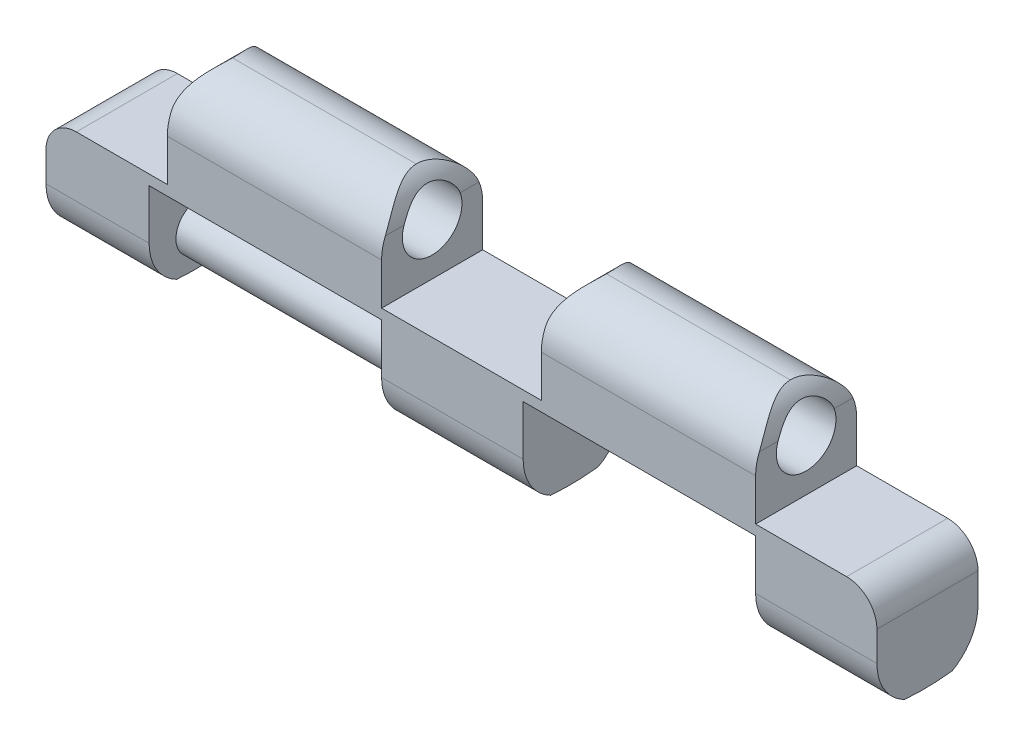
SolidWorks part; units mm, degrees
ref_plane "Alzado" through (0, 0, 0) normal (0, 0, 1) x (1, 0, 0)
ref_plane "Planta" through (0, 0, 0) normal (0, 1, 0) x (1, 0, 0)
ref_plane "Vista lateral" through (0, 0, 0) normal (1, 0, 0) x (0, 0, -1)
sketch "Croquis1" plane through (0, 0, 0) normal (0, 0, 1) x (1, 0, 0)
  line L0 (-11.2351, 0) -> (-5.2351, 0)
  line L1 (-5.2351, 0) -> (-5.2351, 3)
  line L2 (-3.2351, 5) -> (3.3649, 5)
  line L3 (5.3649, 3) -> (5.3649, 0)
  line L4 (5.3649, 0) -> (13.2649, 0)
  line L5 (13.2649, 0) -> (13.2649, 3)
  line L6 (15.2649, 5) -> (21.8649, 5)
  line L7 (23.8649, 3) -> (23.8649, 0)
  line L8 (23.8649, 0) -> (29.8649, 0)
  line L9 (29.8649, 0) -> (29.8649, -6)
  line L10 (29.8649, -6) -> (23.8649, -6)
  line L14 (12.3649, -6) -> (5.3649, -6)
  line L15 (5.3649, -6) -> (5.3649, -0.5)
  line L16 (5.3649, -0.5) -> (-6.1351, -0.5)
  line L17 (-6.1351, -0.5) -> (-6.1351, -6)
  line L18 (-6.1351, -6) -> (-11.2351, -6)
  line L19 (-11.2351, -6) -> (-11.2351, 0)
  line L20 (12.3649, -6) -> (12.3649, -0.5)
  line L21 (12.3649, -0.5) -> (23.8649, -0.5)
  line L22 (23.8649, -0.5) -> (23.8649, -6)
  arc A0 (-5.2351, 3) -> (-3.2351, 5) centre (-3.2351, 3) cw
  arc A1 (3.3649, 5) -> (5.3649, 3) centre (3.3649, 3) cw
  arc A2 (13.2649, 3) -> (15.2649, 5) centre (15.2649, 3) cw
  arc A3 (21.8649, 5) -> (23.8649, 3) centre (21.8649, 3) cw
  point P25 (-5.2351, 5)
  point P28 (5.3649, 5)
  point P31 (13.2649, 5)
  point P34 (23.8649, 5)
  dimension "D14" = 2
  dimension "D15" = 2
  dimension "D16" = 2
  dimension "D17" = 2
  dimension "D1" = 6
  dimension "D2" = 5
  dimension "D3" = 10.6
  dimension "D4" = 5.5
  dimension "D5" = 5
  dimension "D6" = 10.6
  dimension "D7" = 6
  dimension "D10" = 7.9
  dimension "D11" = 6
  dimension "D12" = 6
  dimension "D13" = 11.5
extrude "Saliente-Extruir1" add sketch "Croquis1" along normal blind 5
sketch "Croquis22" plane through (5.3649, 0, 0) normal (1, 0, 0) x (0, 0, -1)
  line L0 (-5, 5) -> (0, 5) construction
  line L2 (-5, 0) -> (-5, 3) construction
  circle A0 centre (-2.5, 2.5) radius 1.475
  dimension "D3" = 2.95
  dimension "D1" = 2.5
  dimension "D2" = 2.5
extrude "Cortar-Extruir19" cut sketch "Croquis22" against normal blind 11.5
sketch "Croquis23" plane through (23.8649, 0, 0) normal (1, 0, 0) x (0, 0, -1)
  line L0 (-5, 5) -> (0, 5) construction
  line L1 (-5, 0) -> (-5, 3) construction
  circle A0 centre (-2.5, 2.5) radius 1.475
  dimension "D1" = 2.95
  dimension "D2" = 2.5
  dimension "D3" = 2.5
extrude "Cortar-Extruir20" cut sketch "Croquis23" against normal blind 11.5
sketch "Croquis24" plane through (23.8649, 0, 0) normal (1, 0, 0) x (0, 0, -1)
  arc A0 (-5.6425, 3.2539) -> (0.6953, 3.2539) centre (-2.4736, 0.085) cw
extrude "Cortar-Extruir21" cut sketch "Croquis24" against normal through all and the other way through all
sketch "Croquis25" plane through (-6.1351, 0, 0) normal (1, 0, 0) x (0, 0, -1)
sketch "Croquis26" plane through (-6.1351, 0, 0) normal (1, 0, 0) x (0, 0, -1)
  line L0 (-5, -0.5) -> (0, -0.5) construction
  line L1 (-5, -6) -> (-5, -0.5) construction
  circle A0 centre (-2.5, -3.45) radius 1.175
  dimension "D3" = 2.35
  dimension "D1" = 2.95
  dimension "D2" = 2.5
sketch "Croquis27" plane through (12.3649, 0, 0) normal (1, 0, 0) x (0, 0, -1)
  line L0 (-5, -0.5) -> (0, -0.5) construction
  line L1 (-5, -6) -> (-5, -0.5) construction
  circle A0 centre (-2.5, -3.45) radius 1.175
  dimension "D3" = 2.35
  dimension "D1" = 2.95
  dimension "D2" = 2.5
sketch "Croquis28" plane through (29.8649, 0, 0) normal (1, 0, 0) x (0, 0, -1)
  arc A0 (-5.5986, -4.9472) -> (0.708, -4.9472) centre (-2.4453, 4.2661) ccw
extrude "Cortar-Extruir23" cut sketch "Croquis28" against normal through all and the other way through all flip side to cut
fillet "Redondeo10" radius 2.5 10 edges at (-8.6851, -5.1308, 5) (-8.6851, -5.1598, 0) (8.8649, -5.1308, 5) (8.8649, -5.1598, 0) (26.8649, -5.1598, 0) (26.8649, -5.1308, 5) (0.0649, 3.7865, 5) (0.0649, 3.822, 0) (18.5649, 3.822, 0) (18.5649, 3.7865, 5)
sketch "Croquis14" plane through (23.8649, 0, 0) normal (1, 0, 0) x (0, 0, -1)
  line L0 (0, 0) -> (0, 2.0664) construction
  line L1 (-5, 0) -> (0, 0) construction
  circle A0 centre (-2.5, 2.5) radius 1.475
  dimension "D1" = 2.95
  dimension "D2" = 2.5
  dimension "D3" = 2.5
fillet "Redondeo6" radius 1.5 2 edges at (29.8649, 0, 2.5) (-11.2351, 0, 2.5)
sketch "Croquis19" plane through (29.8649, 0, 0) normal (1, 0, 0) x (0, 0, -1)
sketch "Croquis21" plane through (29.8649, 0, 0) normal (1, 0, 0) x (0, 0, -1)
  arc A0 (-6.0352, -4.762) -> (0.6431, -4.762) centre (-2.6961, 6.7962) ccw
extrude "Cortar-Extruir18" cut sketch "Croquis21" against normal through all and the other way through all flip side to cut
extrude "Saliente-Extruir2" add sketch "Croquis26" along normal blind 11.5 contours A0
